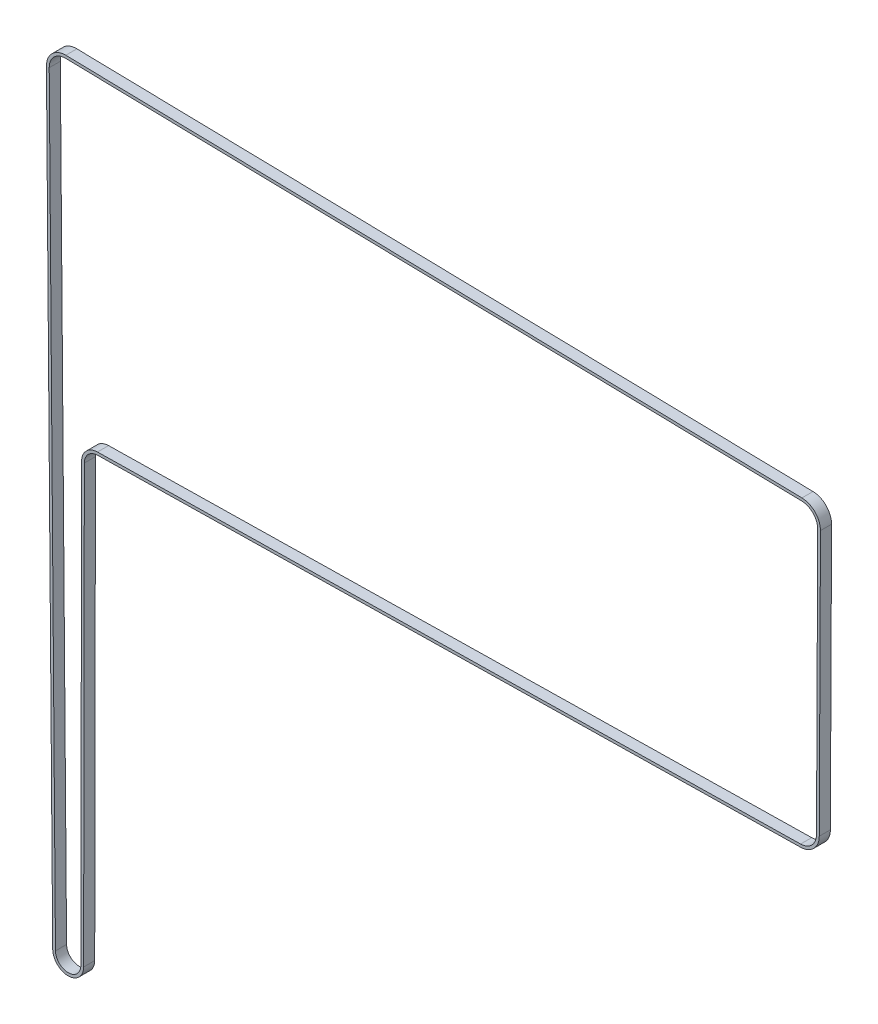
SolidWorks part; units mm, degrees
material "Резина"
ref_plane "Спереди" through (0, 0, 0) normal (0, 0, 1) x (1, 0, 0)
ref_plane "Сверху" through (0, 0, 0) normal (0, 1, 0) x (1, 0, 0)
ref_plane "Справа" through (0, 0, 0) normal (1, 0, 0) x (0, 0, -1)
sketch "Эскиз1" plane through (0, 0, 0) normal (0, 0, 1) x (1, 0, 0)
  line B0 (-6.8585, -0.0565) -> (-10.2497, 411.928)
  line B1 (-1.3179, 420.7481) -> (396.8293, 412.4586)
  line B2 (405.3971, 403.671) -> (404.7499, 260.1848)
  line B3 (396.1496, 251.4756) -> (15.8504, 244.973)
  line B4 (7.25, 236.2388) -> (6.8587, -0.0114)
  arc B5 (6.8587, -0.0114) -> (-6.8585, -0.0565) centre (0, 0) cw
  arc B6 (-10.2497, 411.928) -> (-1.3179, 420.7481) centre (-1.5, 412) cw
  arc B7 (396.8293, 412.4586) -> (405.3971, 403.671) centre (396.6472, 403.7105) cw
  arc B8 (404.7499, 260.1848) -> (396.1496, 251.4756) centre (396, 260.2243) cw
  arc B9 (15.8504, 244.973) -> (7.25, 236.2388) centre (16, 236.2243) ccw
sketch_block_instance "Блок-ремень1-1"
sketch_block "Блок-ремень1"
extrude "Вытянуть-Тонкостенный1" add sketch "Эскиз1" along normal blind 6 thin thin type one direction wall 1.5
